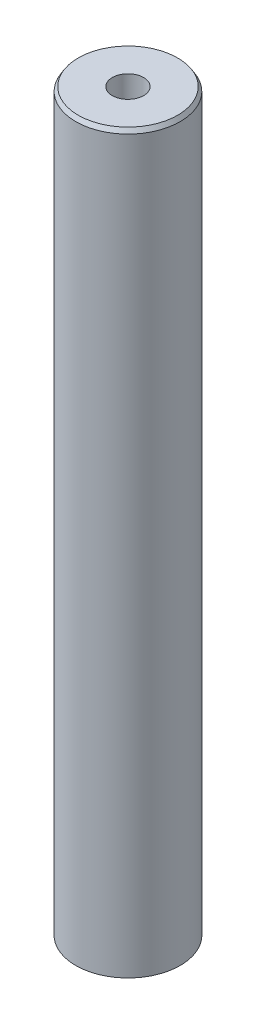
SolidWorks part; units mm, degrees
ref_plane "Front Plane" through (0, 0, 0) normal (0, 0, 1) x (1, 0, 0)
ref_plane "Top Plane" through (0, 0, 0) normal (0, 1, 0) x (1, 0, 0)
ref_plane "Right Plane" through (0, 0, 0) normal (1, 0, 0) x (0, 0, -1)
sketch "Sketch1" plane through (0, 0, 0) normal (0, 1, 0) x (1, 0, 0)
  circle A0 centre (0, 0) radius 42.5
  dimension "SHAFT_OD" = 85
extrude "Boss-Extrude1" add sketch "Sketch1" along normal blind 600
sketch "Sketch2" plane through (0, 0, 0) normal (0, 1, 0) x (1, 0, 0)
  circle A0 centre (0, 0) radius 12.7581
  dimension "BORE_D" = 25.5162
extrude "Cut-Extrude1" cut sketch "Sketch2" along normal through all
chamfer "Chamfer1" distance 3.4562 angle 31.068 2 edges at (0, 600, 42.5) (0, 0, 42.5) first distance on face at (0, 600, 42.5) first distance on face at (0, 0, 12.7581)
